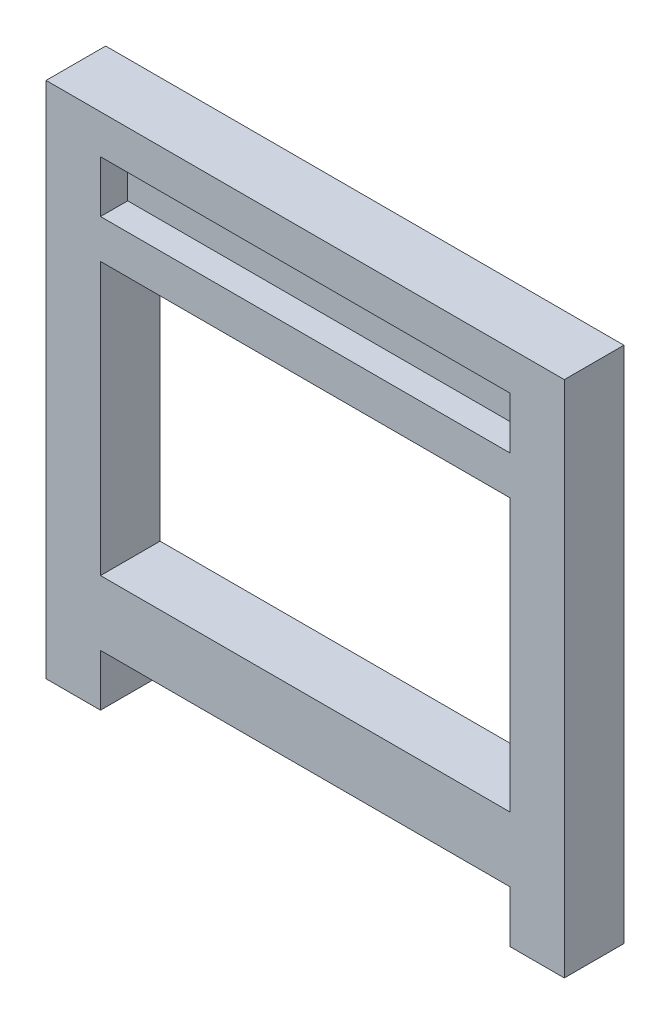
SolidWorks part; units mm, degrees
ref_plane "Front Plane" through (0, 0, 0) normal (0, 0, 1) x (1, 0, 0)
ref_plane "Top Plane" through (0, 0, 0) normal (0, 1, 0) x (1, 0, 0)
ref_plane "Right Plane" through (0, 0, 0) normal (1, 0, 0) x (0, 0, -1)
sketch "Sketch1" plane through (0, 0, 0) normal (0, 0, 1) x (1, 0, 0)
  line L0 (0, 0) -> (0, -2)
  line L1 (2.1, 0) -> (17.9, 0)
  line L2 (0, 0) -> (0, 18)
  line L3 (0, 18) -> (20, 18)
  line L4 (20, 0) -> (20, 18)
  line L5 (0, -2) -> (2.1, -2)
  line L6 (2.1, -2) -> (2.1, 0)
  line L7 (20, 0) -> (20, -2)
  line L8 (20, -2) -> (17.9, -2)
  line L9 (17.9, -2) -> (17.9, 0)
  line L10 (2.1, 0) -> (2.1, 2.5) construction
  line L12 (2.1, 2.5) -> (17.9, 2.5)
  line L13 (2.1, 2.5) -> (2.1, 13)
  line L14 (2.1, 13) -> (17.9, 13)
  line L15 (17.9, 2.5) -> (17.9, 13)
  line L16 (2.1, 14.5) -> (17.9, 14.5)
  line L17 (2.1, 14.5) -> (2.1, 16.5)
  line L18 (2.1, 16.5) -> (17.9, 16.5)
  line L19 (17.9, 14.5) -> (17.9, 16.5)
  dimension "D1" = 18
  dimension "D2" = 20
  dimension "D3" = 2.1
  dimension "D4" = 2
  dimension "D5" = 2
  dimension "D6" = 2.1
  dimension "D7" = 2.5
  dimension "D8" = 10.5
  dimension "D9" = 2
  dimension "D10" = 1.5
  dimension "D11" = 15.8
extrude "Boss-Extrude1" add sketch "Sketch1" along normal blind 2.3
extrude "Boss-Extrude2" add sketch "Sketch1<2>" along normal blind 1.25 contours L16 L19 L18 L17
sketch "Sketch1<2>" plane through (0, 0, 0) normal (0, 0, 1) x (1, 0, 0) same geometry as "Sketch1"
